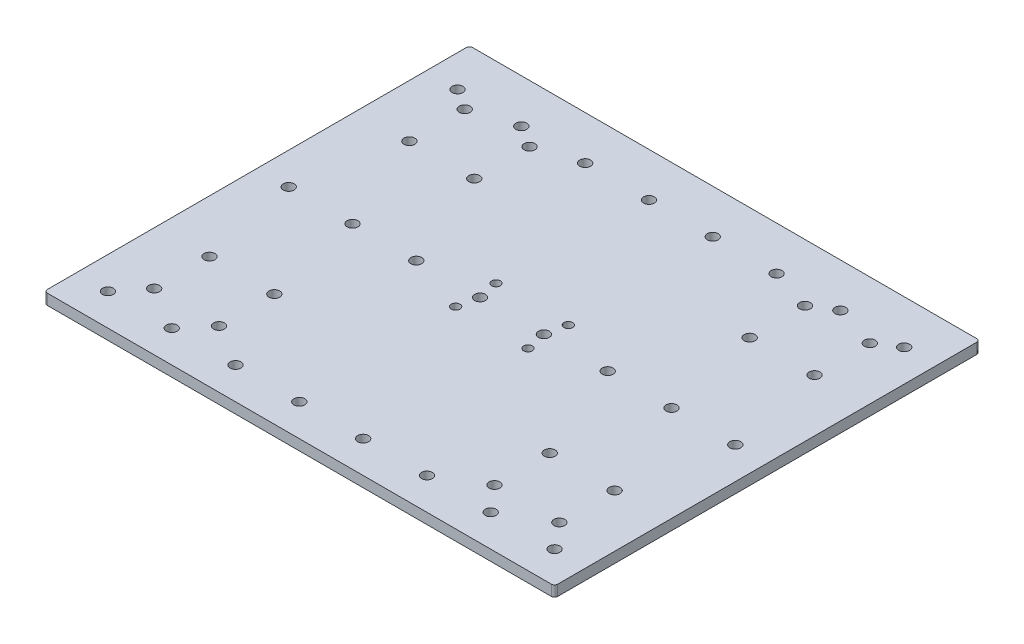
SolidWorks part; units mm, degrees
ref_plane "Front Plane" through (0, 0, 0) normal (0, 0, 1) x (1, 0, 0)
ref_plane "Top Plane" through (0, 0, 0) normal (0, 1, 0) x (1, 0, 0)
ref_plane "Right Plane" through (0, 0, 0) normal (1, 0, 0) x (0, 0, -1)
sketch "Sketch1" plane through (0, 0, 0) normal (0, 1, 0) x (1, 0, 0)
  line L1 (-120, -100) -> (120, -100)
  line L2 (-120, -100) -> (-120, 100)
  line L3 (-120, 100) -> (120, 100)
  line L4 (120, -100) -> (120, 100)
  line L5 (-120, -100) -> (120, 100) construction
  line L6 (-120, 100) -> (120, -100) construction
  point P0 (0, 0)
  dimension "D1" = 240
  dimension "D2" = 200
extrude "Boss-Extrude1" add sketch "Sketch1" along normal mid plane 5
sketch "Sketch2" plane through (0, 2.5, 0) normal (0, 1, 0) x (1, 0, 0)
  line L5 (-80, 100) -> (-80, -100)
  line L6 (-80, 100) -> (-80, -100) construction
  line L8 (80, -100) -> (80, 100)
  line L9 (80, -100) -> (80, 100) construction
  line L11 (120, 60) -> (-120, 60)
  line L12 (120, 60) -> (-120, 60) construction
  line L14 (-120, -60) -> (120, -60)
  line L15 (-120, -60) -> (120, -60) construction
  line L16 (-95.25, 73) -> (-64.75, 73) construction
  line L17 (-95.25, 73) -> (-95.25, 47) construction
  line L18 (-95.25, 47) -> (-64.75, 47) construction
  line L19 (-64.75, 73) -> (-64.75, 47) construction
  line L20 (-95.25, 73) -> (-64.75, 47) construction
  line L21 (-95.25, 47) -> (-64.75, 73) construction
  line L22 (64.75, 47) -> (95.25, 47) construction
  line L23 (64.75, 47) -> (64.75, 73) construction
  line L24 (64.75, 73) -> (95.25, 73) construction
  line L25 (95.25, 47) -> (95.25, 73) construction
  line L26 (64.75, 47) -> (95.25, 73) construction
  line L27 (64.75, 73) -> (95.25, 47) construction
  line L28 (64.75, -47) -> (95.25, -47) construction
  line L29 (64.75, -47) -> (64.75, -73) construction
  line L30 (64.75, -73) -> (95.25, -73) construction
  line L31 (95.25, -47) -> (95.25, -73) construction
  line L32 (64.75, -47) -> (95.25, -73) construction
  line L33 (64.75, -73) -> (95.25, -47) construction
  line L34 (-95.25, -73) -> (-64.75, -73) construction
  line L35 (-95.25, -73) -> (-95.25, -47) construction
  line L36 (-95.25, -47) -> (-64.75, -47) construction
  line L37 (-64.75, -73) -> (-64.75, -47) construction
  line L38 (-95.25, -73) -> (-64.75, -47) construction
  line L39 (-95.25, -47) -> (-64.75, -73) construction
  circle A0 centre (-95.25, 73) radius 2.55
  circle A1 centre (-95.25, 47) radius 2.55
  circle A2 centre (-64.75, 73) radius 2.55
  circle A3 centre (-64.75, 47) radius 2.55
  circle A4 centre (-95.25, -47) radius 2.55
  circle A5 centre (-95.25, -73) radius 2.55
  circle A6 centre (-64.75, -73) radius 2.55
  circle A7 centre (-64.75, -47) radius 2.55
  circle A8 centre (95.25, -47) radius 2.55
  circle A9 centre (64.75, -47) radius 2.55
  circle A10 centre (64.75, -73) radius 2.55
  circle A11 centre (95.25, -73) radius 2.55
  circle A12 centre (64.75, 73) radius 2.55
  circle A13 centre (64.75, 47) radius 2.55
  circle A14 centre (95.25, 73) radius 2.55
  circle A15 centre (95.25, 47) radius 2.55
  point P0 (-80, 60)
  point P13 (80, 60)
  point P18 (80, -60)
  point P23 (-80, -60)
  dimension "D13" = 5.1
  dimension "D14" = 5.1
  dimension "D15" = 5.1
  dimension "D16" = 5.1
  dimension "D17" = 5.1
  dimension "D18" = 5.1
  dimension "D19" = 5.1
  dimension "D20" = 5.1
  dimension "D21" = 5.1
  dimension "D22" = 5.1
  dimension "D23" = 5.1
  dimension "D24" = 5.1
  dimension "D25" = 5.1
  dimension "D26" = 5.1
  dimension "D27" = 5.1
  dimension "D28" = 5.1
  dimension "D1" = 40
  dimension "D5" = 30.5
  dimension "D6" = 26
  dimension "D7" = 30.5
  dimension "D8" = 26
  dimension "D9" = 26
  dimension "D10" = 30.5
  dimension "D11" = 26
  dimension "D12" = 30.5
  dimension "D2" = 40
  dimension "D3" = 40
  dimension "D4" = 40
extrude "Cut-Extrude1" cut sketch "Sketch2" against normal through all
sketch "Sketch3" plane through (0, 2.5, 0) normal (0, 1, 0) x (1, 0, 0)
  line L1 (-17, -9.5) -> (17, -9.5) construction
  line L2 (-17, -9.5) -> (-17, 9.5) construction
  line L3 (-17, 9.5) -> (17, 9.5) construction
  line L4 (17, -9.5) -> (17, 9.5) construction
  line L5 (-17, -9.5) -> (17, 9.5) construction
  line L6 (-17, 9.5) -> (17, -9.5) construction
  circle A0 centre (-17, 9.5) radius 2.05
  circle A1 centre (17, 9.5) radius 2.05
  circle A2 centre (17, -9.5) radius 2.05
  circle A3 centre (-17, -9.5) radius 2.05
  point P0 (0, 0)
  dimension "D3" = 4.1
  dimension "D4" = 4.1
  dimension "D5" = 4.1
  dimension "D6" = 4.1
  dimension "D1" = 34
  dimension "D2" = 19
extrude "Cut-Extrude2" cut sketch "Sketch3" against normal through all
sketch "Sketch4" plane through (0, 2.5, 0) normal (0, 1, 0) x (1, 0, 0)
  line L0 (-105, 100) -> (-105, -100) construction
  line L1 (120, 100) -> (-120, 100) construction
  line L2 (-120, -100) -> (120, -100) construction
  line L3 (-120, 100) -> (-120, -100) construction
  line L4 (-75, 100) -> (-75, -100) construction
  line L5 (-45, 100) -> (-45, -100) construction
  line L6 (-15, 100) -> (-15, -100) construction
  line L7 (15, 100) -> (15, -100) construction
  line L8 (45, 100) -> (45, -100) construction
  line L9 (75, 100) -> (75, -100) construction
  line L10 (105, 100) -> (105, -100) construction
  line L11 (-120, -85) -> (120, -85) construction
  line L12 (-120, 100) -> (-120, -100) construction
  line L13 (120, -100) -> (120, 100) construction
  line L14 (-120, 79.3935) -> (120, 79.3935) construction
  line L15 (-120, 0) -> (120, 0) construction
  circle A0 centre (-105, 79.3935) radius 2.55
  circle A1 centre (-75, 79.3935) radius 2.55
  circle A2 centre (-45, 79.3935) radius 2.55
  circle A3 centre (-15, 79.3935) radius 2.55
  circle A4 centre (15, 79.3935) radius 2.55
  circle A5 centre (45, 79.3935) radius 2.55
  circle A6 centre (75, 79.3935) radius 2.55
  circle A7 centre (105, 79.3935) radius 2.55
  circle A8 centre (-105, 0) radius 2.55
  circle A9 centre (-105, -85) radius 2.55
  circle A10 centre (-75, 0) radius 2.55
  circle A11 centre (-45, 0) radius 2.55
  circle A12 centre (-15, 0) radius 2.55
  circle A13 centre (15, 0) radius 2.55
  circle A14 centre (45, 0) radius 2.55
  circle A15 centre (75, 0) radius 2.55
  circle A16 centre (105, 0) radius 2.55
  circle A17 centre (-75, -85) radius 2.55
  circle A18 centre (-45, -85) radius 2.55
  circle A19 centre (-15, -85) radius 2.55
  circle A20 centre (15, -85) radius 2.55
  circle A21 centre (45, -85) radius 2.55
  circle A22 centre (75, -85) radius 2.55
  circle A23 centre (105, -85) radius 2.55
  point P6 (-120, 0)
  dimension "D3" = 5.1
  dimension "D4" = 5.1
  dimension "D5" = 5.1
  dimension "D1" = 15
  dimension "D2" = 15
extrude "Cut-Extrude3" cut sketch "Sketch4" against normal through all
fillet "Fillet1" radius 1.5 4 edges at (-120, 0, -100) (120, 0, -100) (-120, 0, 100) (120, 0, 100)
